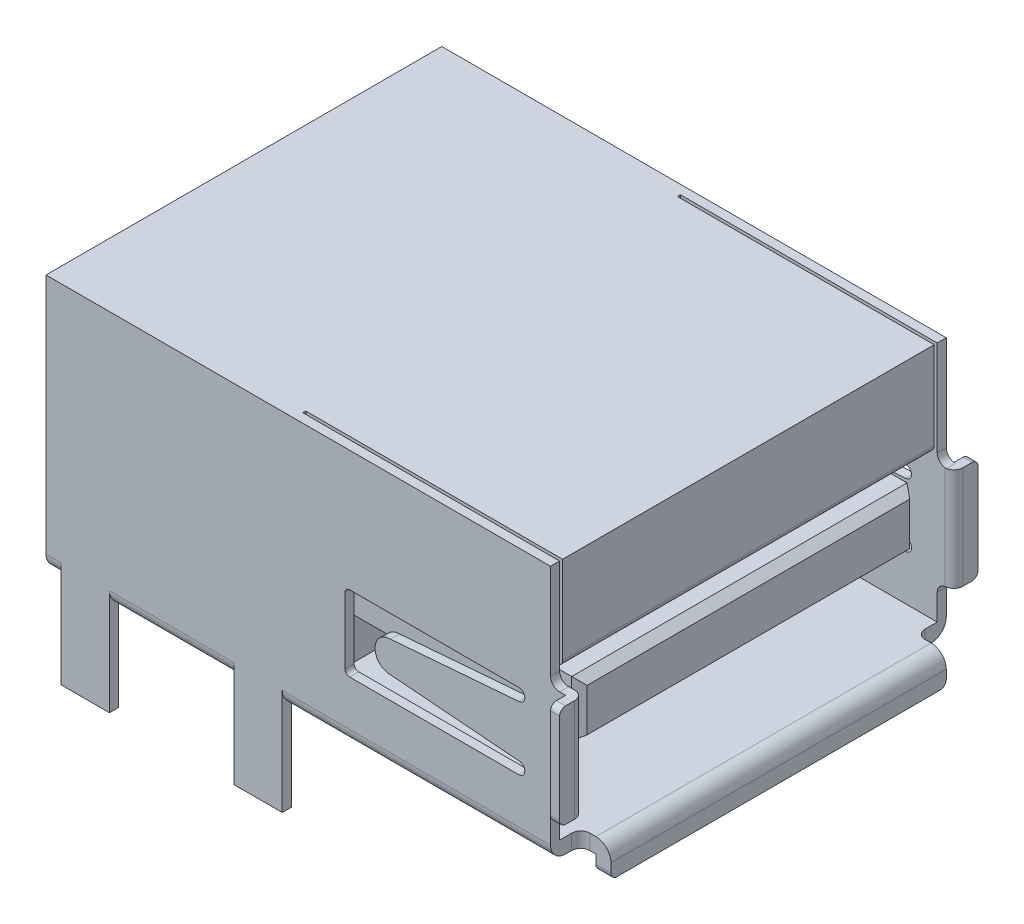
SolidWorks part; units mm, degrees
material "ABS"
ref_plane "Plan de face" through (0, 0, 0) normal (0, 0, 1) x (1, 0, 0)
ref_plane "Plan de dessus" through (0, 0, 0) normal (0, 1, 0) x (1, 0, 0)
ref_plane "Plan de droite" through (0, 0, 0) normal (1, 0, 0) x (0, 0, -1)
sketch "Esquisse1" plane through (0, 0, 0) normal (0, 0, 1) x (1, 0, 0)
  line L0 (0, 0) -> (0, 8.5)
  line L1 (0, 8.5) -> (16.7, 8.5)
  line L2 (16.7, 8.5) -> (16.7, 0.5)
  line L3 (16.7, 0.5) -> (17.2, 0.5)
  line L4 (17.2, 0.5) -> (17.2, 0)
  line L5 (17.2, 0) -> (7.82, 0)
  line L6 (7.82, 0) -> (7.82, -3)
  line L7 (7.82, -3) -> (6.22, -3)
  line L8 (6.22, -3) -> (6.22, 0)
  line L9 (6.22, 0) -> (2.1, 0)
  line L10 (2.1, 0) -> (2.1, -3)
  line L11 (2.1, -3) -> (0.5, -3)
  line L12 (0.5, -3) -> (0.5, 0)
  line L13 (0.5, 0) -> (0, 0)
  dimension "D1" = 16.7
  dimension "D2" = 8.5
  dimension "D3" = 0.5
  dimension "D4" = 0.5
  dimension "D5" = 1.6
  dimension "D6" = 0.5
  dimension "D7" = 1.6
  dimension "D8" = 4.12
  dimension "D9" = 3
  dimension "D10" = 3
extrude "Boss.-Extru.1" add sketch "Esquisse1" along normal blind 13.1
sketch "Esquisse2" plane through (0.5, 0, 0) normal (-1, 0, 0) x (0, 0, 1)
  line L0 (13.1, -3) -> (0, -3) construction
  line L1 (0.3, 0) -> (12.8, 0)
  line L2 (0.3, 0) -> (0.3, -3)
  line L3 (0.3, -3) -> (12.8, -3)
  line L4 (12.8, 0) -> (12.8, -3)
  line L5 (0, 0) -> (0, -3) construction
  line L6 (13.1, 0) -> (0, 0) construction
  line L7 (13.1, 0) -> (13.1, -3) construction
  dimension "D1" = 0.3
  dimension "D2" = 0
  dimension "D3" = 0.3
extrude "Enlèv. mat.-Extru.1" cut sketch "Esquisse2" against normal blind 7.4
sketch "Esquisse3" plane through (16.7, 0, 0) normal (1, 0, 0) x (0, 0, -1)
  line L0 (-13.1, 0) -> (0, 0) construction
  line L1 (-12.1, 2.85) -> (-1, 2.85)
  line L2 (-12.1, 2.85) -> (-12.1, 4.69)
  line L3 (-12.1, 4.69) -> (-1, 4.69)
  line L4 (-1, 2.85) -> (-1, 4.69)
  line L5 (-12.1, 2.85) -> (-1, 4.69) construction
  line L6 (-12.1, 4.69) -> (-1, 2.85) construction
  line L7 (0, 0.5) -> (0, 8.5) construction
  line L8 (-13.1, 0.5) -> (-13.1, 8.5) construction
  line L9 (-12.8, 8.5) -> (-12.8, 0.5)
  line L10 (-13.1, 8.5) -> (0, 8.5) construction
  line L11 (-12.8, 0.5) -> (-0.3, 0.5)
  line L12 (-0.3, 0.5) -> (-0.3, 8.5)
  line L13 (-0.3, 8.5) -> (-0.4, 8.5)
  line L14 (-0.4, 8.5) -> (-0.4, 5.4)
  line L15 (-0.4, 5.4) -> (-12.7, 5.4)
  line L16 (-12.7, 5.4) -> (-12.7, 8.5)
  line L17 (-12.7, 8.5) -> (-12.8, 8.5)
  point P0 (-6.55, 3.77)
  point P9 (0, 4.5)
  dimension "D1" = 2.85
  dimension "D2" = 1
  dimension "D3" = 1
  dimension "D4" = 1.84
  dimension "D5" = 0.3
  dimension "D6" = 0.3
  dimension "D7" = 0.5
  dimension "D8" = 3.1
  dimension "D9" = 0.1
  dimension "D10" = 0.1
extrude "Enlèv. mat.-Extru.2" cut sketch "Esquisse3" against normal blind 8.5
sketch "Esquisse4" plane through (16.7, 0, 0) normal (1, 0, 0) x (0, 0, -1)
  line L0 (-12.8, 8.5) -> (-12.8, 0.5) construction
  line L1 (-13.1, 1.65) -> (-12.8, 1.65)
  line L2 (-13.1, 1.65) -> (-13.1, 5.05)
  line L3 (-13.1, 5.05) -> (-12.8, 5.05)
  line L4 (-12.8, 1.65) -> (-12.8, 5.05)
  line L5 (-13.1, 0.5) -> (-13.1, 8.5) construction
  line L6 (-13.1, 0) -> (0, 0) construction
  dimension "D1" = 3.4
  dimension "D2" = 1.65
extrude "Boss.-Extru.2" add sketch "Esquisse4" along normal blind 0.5
ref_plane "Plan2" through (17.2, 1.65, 13.1) normal (0, -1, 0) x (1, 0, 0)
sketch "Esquisse8" plane through (17.2, 1.65, 13.1) normal (0, -1, 0) x (1, 0, 0)
  line L0 (0, 0) -> (0, 0.5)
  line L2 (0, 0.5) -> (0.3, 0.5)
  line L3 (0.3, 0.5) -> (0.3, 0)
  line L8 (-0.5, 0) -> (-0.5, -0.3)
  line L9 (-0.5, -0.3) -> (0, -0.3)
  line L10 (0, -0.3) -> (0, 0)
  line L11 (0, 0) -> (-0.5, 0)
  line L14 (0, -0.3) -> (0, 0)
  arc A0 (0, -0.3) -> (0.3, 0) centre (0, 0) ccw
  dimension "D1" = 0.3
  dimension "D2" = 0.5
  dimension "D3" = 0
extrude "Boss.-Extru.3" add sketch "Esquisse8" against normal blind 3.4
sketch "Esquisse9" plane through (17.2, 1.65, 13.1) normal (0, -1, 0) x (1, 0, 0)
  line L0 (-0.5, -13.1) -> (-0.25, -13.1)
  line L1 (0, -13.1) -> (-0.5, -13.1) construction
  line L2 (-0.25, -13.1) -> (-0.25, -13.6)
  line L3 (-0.25, -13.6) -> (0.05, -13.6)
  line L4 (0.05, -13.6) -> (0.05, -13.1)
  line L5 (-0.5, -12.8) -> (-0.25, -12.8)
  line L6 (-0.5, -13.1) -> (-0.5, -12.8)
  line L7 (-0.5, -12.8) -> (-0.4861, -12.8085)
  arc A0 (0.05, -13.1) -> (-0.25, -12.8) centre (-0.25, -13.1) ccw
  dimension "D1" = 0.3
  dimension "D2" = 0.5
extrude "Boss.-Extru.4" add sketch "Esquisse9" against normal blind 3.4 contours L6 L0 L2 L3 L4 A0 L5
chamfer "Chanfrein1" distance 0.3 angle 35 1 edges at (16.7, 4.69, 6.55)
chamfer "Chanfrein2" distance 0.3 angle 35 1 edges at (16.7, 3.665, 1)
chamfer "Chanfrein3" distance 0.3 angle 35 2 edges at (16.7, 3.665, 12.1) (16.7, 2.85, 6.655)
fillet "Congé1" radius 0.2 1 edges at (16.7, 5.4, 6.55)
fillet "Congé2" radius 0.2 4 edges at (17.1, 1.65, -0.5) (17.1, 5.05, -0.5) (17.35, 1.65, 13.6) (17.35, 5.05, 13.6)
sketch "Esquisse10" plane through (0, 0, 0) normal (0, 0, -1) x (-1, 0, 0)
  line L1 (-16.7, 0.5) -> (-17.2, 0.5)
  line L2 (-16.7, 0.5) -> (-16.7, 0)
  line L3 (-16.7, 0) -> (-17.2, 0)
  line L4 (-17.2, 0.5) -> (-17.2, 0)
extrude "Enlèv. mat.-Extru.3" cut sketch "Esquisse10" against normal blind 1
sketch "Esquisse11" plane through (0, 0, 13.1) normal (0, 0, 1) x (1, 0, 0)
  line L0 (17.2, 0.5) -> (16.7, 0.5) construction
  line L1 (17.2, 0.5) -> (16.7, 0.5)
  line L2 (17.2, 0.5) -> (17.2, 0)
  line L3 (17.2, 0) -> (16.7, 0)
  line L4 (16.7, 0.5) -> (16.7, 0)
  line L5 (17.2, 0) -> (17.2, 0.5) construction
  line L6 (7.82, 0) -> (17.2, 0) construction
  line L7 (16.7, 0.5) -> (16.7, 1.65) construction
extrude "Enlèv. mat.-Extru.4" cut sketch "Esquisse11" against normal blind 1
ref_plane "Plan3" through (0, 0, 12.1) normal (0, 0, 1) x (1, 0, 0)
sketch "Esquisse12" plane through (0, 0, 12.1) normal (0, 0, 1) x (1, 0, 0)
  line L0 (17.2, 0) -> (17.2, -0.5)
  line L1 (16.7, 0) -> (17.2, 0) construction
  line L4 (17.2, 0) -> (17.2, 0.5) construction
  line L5 (17.2, 0.5) -> (17.2, 0)
  line L6 (17.2, -0.5) -> (17.7, -0.5)
  line L7 (17.7, -0.5) -> (17.7, 0)
  arc A0 (17.2, 0.5) -> (17.7, 0) centre (17.2, 0) cw
  dimension "D3" = 0.5
  dimension "D1" = 0.5
  dimension "D2" = 0.5
extrude "Boss.-Extru.5" add sketch "Esquisse12" against normal blind 11.1
fillet "Congé3" radius 0.5 1 edges at (12.26, 0, 13.1)
fillet "Congé4" radius 0.5 2 edges at (7.02, 0, 0.3) (12.26, 0, 0)
sketch "Esquisse13" plane through (0, 0, 13.1) normal (0, 0, 1) x (1, 0, 0)
  line L0 (9.9, 4.35) -> (9.9, 2.15)
  line L1 (10.05, 2) -> (15.65, 2)
  line L2 (11.4, 3.76) -> (15.65, 4.1)
  line L3 (11.4, 2.74) -> (15.65, 2.4)
  line L4 (10.05, 4.5) -> (15.65, 4.5)
  line L5 (0, 8.5) -> (0, 0.5) construction
  line L6 (7.82, 0.5) -> (16.7, 0.5) construction
  arc A0 (10.05, 4.5) -> (9.9, 4.35) centre (10.05, 4.35) ccw
  arc A1 (10.05, 2) -> (9.9, 2.15) centre (10.05, 2.15) cw
  arc A2 (11.4, 3.76) -> (11.4, 2.74) centre (11.4, 3.25) ccw
  arc A3 (15.65, 4.5) -> (15.65, 4.1) centre (15.65, 4.3) cw
  arc A4 (15.65, 2.4) -> (15.65, 2) centre (15.65, 2.2) cw
  dimension "D2" = 0.15
  dimension "D3" = 0.51
  dimension "D4" = 1.5
  dimension "D5" = 1.25
  dimension "D6" = 0.4
  dimension "D7" = 9.9
  dimension "D8" = 0.2
  dimension "D12" = 5.6
  dimension "D11" = 0.2
  dimension "D15" = 0.15
  dimension "D9" = 1.5
  dimension "D10" = 5.6
  dimension "D13" = 0.15
  dimension "D14" = 2.5
extrude "Enlèv. mat.-Extru.5" cut sketch "Esquisse13" against normal blind 0.3
sketch "Esquisse14" plane through (0, 0, 0) normal (0, 0, -1) x (-1, 0, 0)
  line L0 (-15.65, 4.5) -> (-10.05, 4.5)
  line L1 (-9.9, 4.35) -> (-9.9, 2.15)
  line L2 (-10.05, 2) -> (-15.65, 2)
  line L3 (-16.7, 0.5) -> (-7.82, 0.5) construction
  line L4 (0, 8.5) -> (0, 0.5) construction
  line L5 (-15.65, 2.4) -> (-11.4, 2.74) construction
  line L6 (-11.4, 3.76) -> (-15.65, 4.1)
  line L7 (-15.65, 2.4) -> (-11.4, 2.74)
  arc A0 (-10.05, 2) -> (-9.9, 2.15) centre (-10.05, 2.15) ccw
  arc A1 (-9.9, 4.35) -> (-10.05, 4.5) centre (-10.05, 4.35) ccw
  arc A2 (-15.65, 4.5) -> (-15.65, 4.1) centre (-15.65, 4.3) ccw
  arc A5 (-15.65, 2) -> (-15.65, 2.4) centre (-15.65, 2.2) cw
  arc A6 (-11.4, 3.76) -> (-11.4, 2.74) centre (-11.4, 3.25) cw
  point P12 (-9.9, 4.5)
  dimension "D5" = 0.15
  dimension "D1" = 2.5
  dimension "D2" = 1.5
  dimension "D3" = 9.9
extrude "Enlèv. mat.-Extru.6" cut sketch "Esquisse14" against normal blind 0.3
fillet "Congé5" radius 0.2 2 edges at (17.45, -0.5, 1) (17.45, -0.5, 12.1)
fillet "Congé6" radius 0.3 9 edges at (16.7, 5.05, 12.95) (16.7, 1.65, 12.95) (16.825, 1.65, 0.3) (16.7, 1.65, 0.15) (16.825, 5.05, 0.3) (16.7, 5.05, 0.15) (16.7, 0.25, 1) (16.7, 0.25, 12.1)
